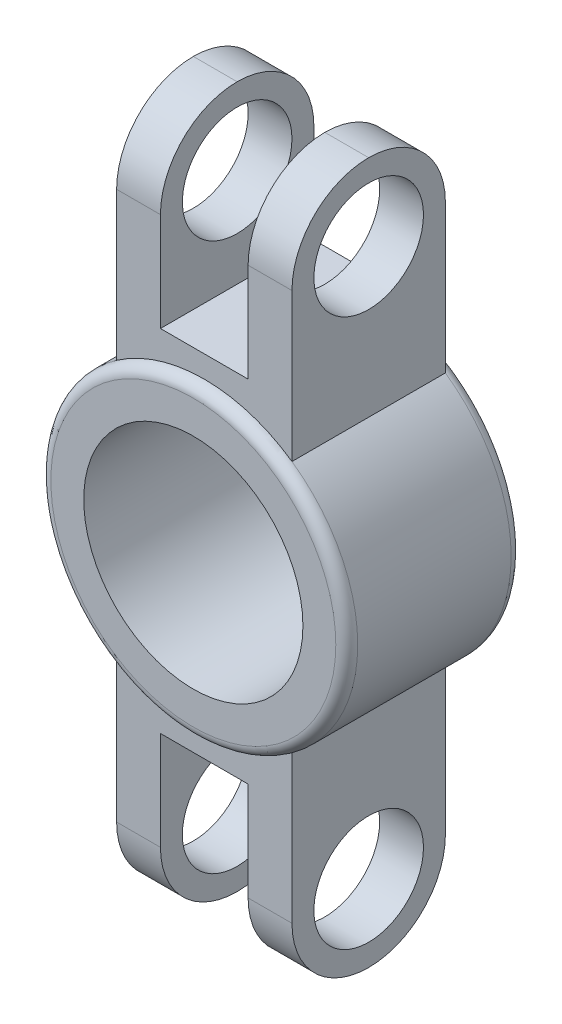
SolidWorks part; units mm, degrees
ref_plane "Front Plane" through (0, 0, 0) normal (0, 0, 1) x (1, 0, 0)
ref_plane "Top Plane" through (0, 0, 0) normal (0, 1, 0) x (1, 0, 0)
ref_plane "Right Plane" through (0, 0, 0) normal (1, 0, 0) x (0, 0, -1)
sketch "Sketch1" plane through (0, 0, 0) normal (0, 0, 1) x (1, 0, 0)
  circle A0 centre (0, 0) radius 6.35
  circle A1 centre (0, 0) radius 8.89
  dimension "D1" = 12.7
  dimension "D2" = 17.78
extrude "Boss-Extrude1" add sketch "Sketch1" along normal mid plane 10.16
fillet "Fillet1" radius 0.635 2 edges at (8.89, 0, -5.08) (8.89, 0, 5.08)
sketch "Sketch2" plane through (0, 0, 0) normal (1, 0, 0) x (0, 0, -1)
  line L0 (5.08, 6.35) -> (-5.08, 6.35) construction
  line L1 (-4.445, 6.35) -> (4.445, 6.35)
  line L2 (-4.445, 6.35) -> (-4.445, 10.16)
  line L3 (-4.445, 10.16) -> (4.445, 10.16)
  line L4 (4.445, 6.35) -> (4.445, 10.16)
  line L6 (-4.445, -8.89) -> (-4.445, 8.89) construction
  line L7 (4.445, 8.89) -> (4.445, -8.89) construction
  dimension "D1" = 3.81
extrude "Boss-Extrude2" add sketch "Sketch2" along normal mid plane 7.62
sketch "Sketch3" plane through (0, 10.16, 0) normal (0, 1, 0) x (1, 0, 0)
  line L0 (3.81, 4.445) -> (3.81, -4.445) construction
  line L1 (2.54, -4.445) -> (5.08, -4.445)
  line L2 (2.54, -4.445) -> (2.54, 4.445)
  line L3 (2.54, 4.445) -> (5.08, 4.445)
  line L4 (5.08, -4.445) -> (5.08, 4.445)
  line L5 (2.54, -4.445) -> (5.08, 4.445) construction
  line L6 (2.54, 4.445) -> (5.08, -4.445) construction
  line L7 (-3.81, 4.445) -> (-3.81, -4.445) construction
  line L8 (-5.08, -4.445) -> (-2.54, -4.445)
  line L9 (-5.08, -4.445) -> (-5.08, 4.445)
  line L10 (-5.08, 4.445) -> (-2.54, 4.445)
  line L11 (-2.54, -4.445) -> (-2.54, 4.445)
  line L12 (-5.08, -4.445) -> (-2.54, 4.445) construction
  line L13 (-5.08, 4.445) -> (-2.54, -4.445) construction
  line L14 (3.81, 4.445) -> (-3.81, 4.445) construction
  point P0 (3.81, 0)
  point P7 (-3.81, 0)
  dimension "D1" = 5.08
extrude "Boss-Extrude3" add sketch "Sketch3" along normal blind 10.16 and the other way blind 3.175
fillet "Fillet2" radius 4.445 4 edges at (-3.81, 20.32, -4.445) (-3.81, 20.32, 4.445) (3.81, 20.32, -4.445) (3.81, 20.32, 4.445)
sketch "Sketch4" plane through (5.08, 0, 0) normal (1, 0, 0) x (0, 0, -1)
  circle A0 centre (0, 15.875) radius 3.175
  arc A1 (0, 20.32) -> (-4.445, 15.875) centre (0, 15.875) ccw construction
  dimension "D1" = 6.35
extrude "Cut-Extrude1" cut sketch "Sketch4" against normal blind 10.16
mirror "Mirror1" about plane through (0, 0, 0) normal (0, 1, 0) of "Cut-Extrude1", "Fillet2", "Boss-Extrude3", "Boss-Extrude2"
